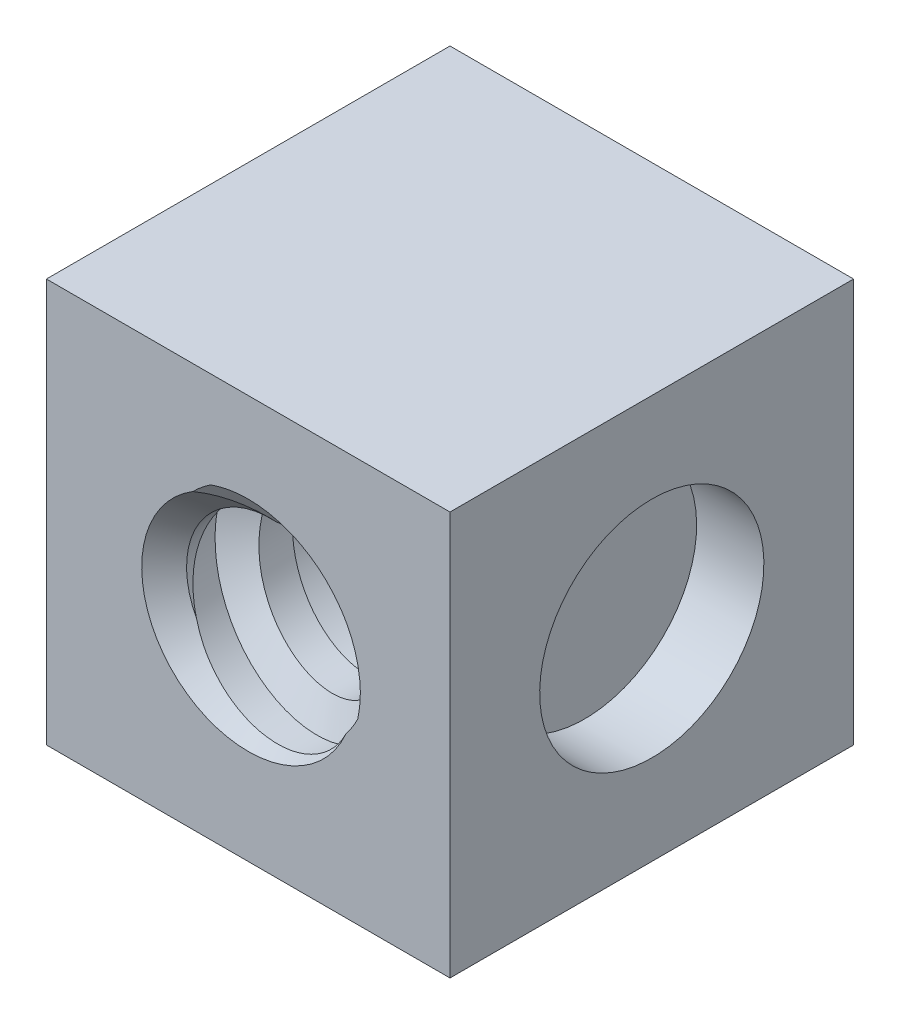
SolidWorks part; units mm, degrees
ref_plane "Front Plane" through (0, 0, 0) normal (0, 0, 1) x (1, 0, 0)
ref_plane "Top Plane" through (0, 0, 0) normal (0, 1, 0) x (1, 0, 0)
ref_plane "Right Plane" through (0, 0, 0) normal (1, 0, 0) x (0, 0, -1)
sketch "Sketch1" plane through (0, 0, 0) normal (0, 0, 1) x (1, 0, 0)
  line L1 (-9, 9) -> (9, 9)
  line L2 (-9, 9) -> (-9, -9)
  line L3 (-9, -9) -> (9, -9)
  line L4 (9, 9) -> (9, -9)
  line L5 (-9, 9) -> (9, -9) construction
  line L6 (-9, -9) -> (9, 9) construction
  circle A0 centre (0, 0) radius 3.75
  point P0 (0, 0)
  dimension "D3" = 7.5
  dimension "D1" = 18
  dimension "D2" = 18
extrude "Boss-Extrude1" add sketch "Sketch1" along normal blind 18
sketch "Sketch2" plane through (9, 0, 0) normal (1, 0, 0) x (0, 0, -1)
  line L0 (-18, -9) -> (0, -9) construction
  circle A0 centre (-9, 0) radius 5
  point P5 (-9, -9)
  dimension "D1" = 10
extrude "Cut-Extrude1" cut sketch "Sketch2" against normal blind 3
mirror "Mirror1" about plane through (0, 0, 0) normal (1, 0, 0) of "Cut-Extrude1"
sketch "Sketch3" plane through (0, 0, 0) normal (1, 0, 0) x (0, 0, -1)
  line L0 (2.2217, -5) -> (2.9434, -3.75)
  line L1 (2.9434, -3.75) -> (0, -3.75)
  line L2 (0, -3.75) -> (0.7217, -5)
  line L3 (0.7217, -5) -> (2.2217, -5)
  line L4 (1.4717, -3.75) -> (1.4717, -7.4531) construction
  line L5 (0, -3.75) -> (0, 3.75) construction
  dimension "D1" = 60
  dimension "D2" = 1.25
  dimension "D3" = 1.5
  dimension "D4" = 3.75
sketch "Sketch4" plane through (0, 0, 0) normal (0, 0, -1) x (-1, 0, 0)
  circle A0 centre (0, 0) radius 3.75 construction
  circle A1 centre (0, 0) radius 3.75
curve "Helix/Spiral1" pitch 4.44 height 22 radius 3.75 centre (0, 0, 0) axis (0, 0, 1) start towards (-1, 0, 0)
sweep "Cut-Sweep2" cut profiles "Sketch3" path "Helix/Spiral1" align with end faces yes
chamfer "Chamfer1" distance 1 angle 45 1 edges
chamfer "Chamfer2" distance 1 angle 45 1 edges
